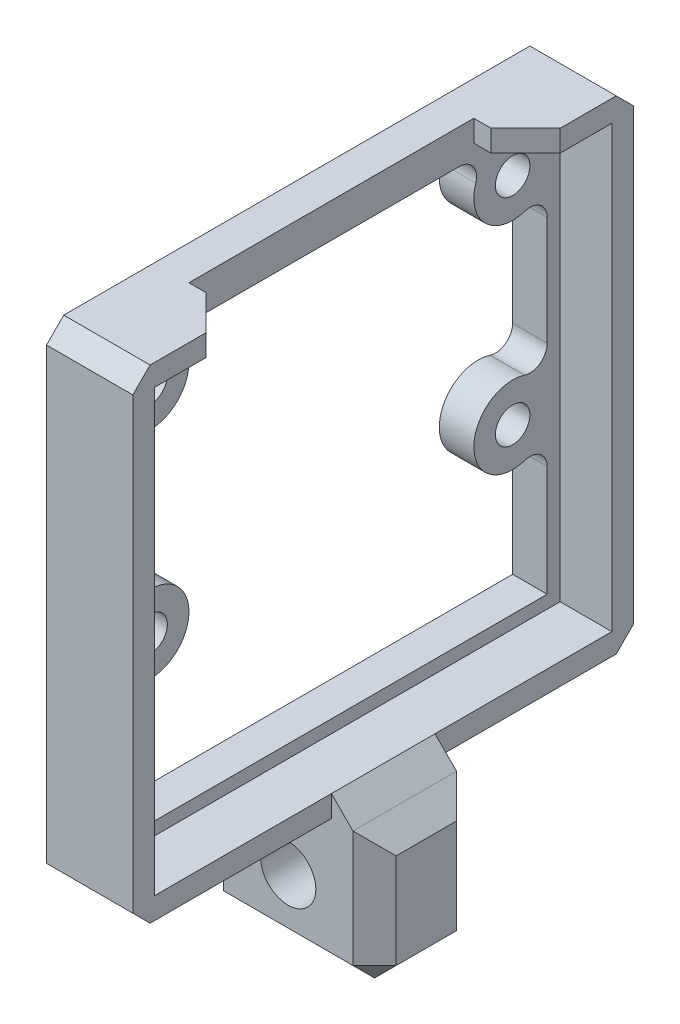
SolidWorks part; units mm, degrees
ref_plane "Front Plane" through (0, 0, 0) normal (0, 0, 1) x (1, 0, 0)
ref_plane "Top Plane" through (0, 0, 0) normal (0, 1, 0) x (1, 0, 0)
ref_plane "Right Plane" through (0, 0, 0) normal (1, 0, 0) x (0, 0, -1)
sketch "Sketch1" plane through (0, 0, 0) normal (1, 0, 0) x (0, 0, -1)
  line L0 (10.4772, -6.2072) -> (-10.5228, -6.2072) construction
  line L1 (10.4772, -6.2072) -> (10.4772, 6.2928) construction
  line L2 (10.4772, 6.2928) -> (-10.5228, 6.2928) construction
  line L3 (-10.5228, -6.2072) -> (-10.5228, 6.2928) construction
  line L4 (10.4772, -6.2072) -> (-10.5228, 6.2928) construction
  line L5 (-12.5228, 5.262) -> (-12.5228, -5.1764)
  line L6 (-12.5228, -7.238) -> (-12.5228, -13.7072)
  line L7 (-10.5228, -15.7072) -> (10.4772, -15.7072)
  line L8 (12.4772, -13.7072) -> (12.4772, -7.238)
  line L9 (12.4772, -5.1764) -> (12.4772, 5.262)
  line L10 (9.4464, 8.2928) -> (-9.4921, 8.2928)
  line L11 (10.4772, 6.2928) -> (-10.5228, -6.2072) construction
  line L12 (-14.5228, 10.2928) -> (-14.5228, -17.7072)
  line L13 (-12.5228, 8.2928) -> (12.4772, 8.2928)
  line L14 (-12.5228, 8.2928) -> (-12.5228, -15.7072)
  line L15 (-12.5228, -15.7072) -> (12.4772, -15.7072)
  line L16 (12.4772, 8.2928) -> (12.4772, -15.7072)
  line L17 (-12.5228, 8.2928) -> (12.4772, -15.7072) construction
  line L18 (-12.5228, -15.7072) -> (12.4772, 8.2928) construction
  line L19 (-14.5228, -17.7072) -> (14.4772, -17.7072)
  line L20 (14.4772, 10.2928) -> (14.4772, -17.7072)
  line L21 (-14.5228, 10.2928) -> (14.4772, 10.2928)
  circle A0 centre (10.4772, 6.2928) radius 1
  circle A1 centre (-10.5228, 6.2928) radius 1
  arc A2 (-12.5228, 5.262) -> (-9.4921, 8.2928) centre (-10.5228, 6.2928) ccw
  arc A3 (-12.5228, -7.238) -> (-12.5228, -5.1764) centre (-10.5228, -6.2072) ccw
  arc A4 (-12.5228, -13.7072) -> (-10.5228, -15.7072) centre (-10.5228, -13.7072) ccw
  arc A5 (10.4772, -15.7072) -> (12.4772, -13.7072) centre (10.4772, -13.7072) ccw
  arc A6 (12.4772, -5.1764) -> (12.4772, -7.238) centre (10.4772, -6.2072) ccw
  arc A7 (9.4464, 8.2928) -> (12.4772, 5.262) centre (10.4772, 6.2928) ccw
  circle A8 centre (-10.5228, -6.2072) radius 1
  circle A9 centre (10.4772, -6.2072) radius 1
  point P22 (-0.0228, 0.0428)
  point P28 (-0.0228, -3.7072)
  dimension "D1" = 2
  dimension "D2" = 2.25
  dimension "D3" = 2
  dimension "D4" = 9.4464
  dimension "D5" = 12.4772
  dimension "D6" = 0.0228
  dimension "D7" = 0.0428
  dimension "D8" = 5.262
  dimension "D9" = 15.7072
  dimension "D10" = 2
extrude "Boss-Extrude1" add sketch "Sketch1" along normal blind 2 contours L21 L12 L19 L20 L13 L16 L9 L8 L15 L7 L14 L6 L5 L10 | L14 A3 A8 | A1 | L14 A2 L13 A1 | L13 A7 L16 A0 | L16 A6 A9
sketch "Sketch2" plane through (2, 0, 0) normal (1, 0, 0) x (0, 0, -1)
  line L1 (-13.2728, 9.0428) -> (13.2272, 9.0428)
  line L2 (-13.2728, 9.0428) -> (-13.2728, -16.4572)
  line L3 (-13.2728, -16.4572) -> (13.2272, -16.4572)
  line L4 (14.4772, 10.2928) -> (-14.5228, 10.2928)
  line L5 (-14.5228, 10.2928) -> (-14.5228, -17.7072)
  line L6 (-14.5228, -17.7072) -> (14.4772, -17.7072)
  line L7 (14.4772, -17.7072) -> (14.4772, 10.2928)
  line L8 (14.4772, 10.2928) -> (-14.5228, 10.2928)
  line L9 (-14.5228, 10.2928) -> (-14.5228, -17.7072)
  line L10 (-14.5228, -17.7072) -> (14.4772, -17.7072)
  line L11 (14.4772, -17.7072) -> (14.4772, 10.2928)
  line L12 (13.2272, 9.0428) -> (13.2272, -16.4572)
  line L13 (-13.2728, 9.0428) -> (13.2272, -16.4572) construction
  line L14 (-13.2728, -16.4572) -> (13.2272, 9.0428) construction
  point P8 (-0.0228, -3.7072)
  dimension "D2" = 25.5
  dimension "D3" = 26.5
  dimension "D4" = 1.25
  dimension "D5" = 1.25
  dimension "D1" = 0
extrude "Boss-Extrude2" add sketch "Sketch2" along normal blind 3
fillet "Fillet1" radius 1 8 edges at (1, -5.1764, 12.5228) (1, -7.238, 12.5228) (1, 5.262, 12.5228) (1, 8.2928, 9.4921) (1, 8.2928, -9.4464) (1, 5.262, -12.4772) (1, -7.238, -12.4772) (1, -5.1764, -12.4772)
sketch "Sketch3" plane through (0, 0, 0) normal (-1, 0, 0) x (0, 0, 1)
  line L0 (14.5228, -17.7072) -> (-14.4772, -17.7072) construction
  line L1 (-2.9772, -17.7072) -> (3.0228, -17.7072)
  line L2 (-2.9772, -17.7072) -> (-2.9772, -25.7072)
  line L3 (-2.9772, -25.7072) -> (3.0228, -25.7072)
  line L4 (3.0228, -17.7072) -> (3.0228, -25.7072)
  line L5 (-2.9772, -17.7072) -> (3.0228, -25.7072) construction
  line L6 (-2.9772, -25.7072) -> (3.0228, -17.7072) construction
  point P4 (0.0228, -21.7072)
  point P7 (13.9832, -21.7072)
  point P8 (0.0228, -17.7072)
  point P9 (0.0228, -17.7072)
  dimension "D1" = 8
  dimension "D2" = 6
extrude "Boss-Extrude3" add sketch "Sketch3" along normal blind 2.5 and the other way blind 7.5
chamfer "Chamfer1" distance 1.25 angle 45 12 edges at (2.5, -25.7072, -2.9772) (-2.5, -17.7072, 0.0228) (-2.5, -21.7072, 3.0228) (-2.5, -21.7072, -2.9772) (-2.5, -25.7072, 0.0228) (2.5, -25.7072, 3.0228) (7.5, -25.7072, 0.0228) (7.5, -21.7072, 3.0228) (7.5, -17.7072, 0.0228) (7.5, -21.7072, -2.9772) (5, -17.7072, 0.0228) (0, -17.7072, 0.0228)
sketch "Sketch5" plane through (0, 0, -2.9772) normal (0, 0, -1) x (-1, 0, 0)
  line L0 (2.5, -18.9572) -> (2.5, -24.4572) construction
  line L1 (1.25, -25.7072) -> (-6.25, -25.7072) construction
  circle A0 centre (-2.5, -21.7072) radius 1.6
  dimension "D1" = 3.2
  dimension "D2" = 5
  dimension "D3" = 4
extrude "Cut-Extrude1" cut sketch "Sketch5" against normal through all both and the other way through all
sketch "Sketch7" plane through (0, 9.0428, 0) normal (0, -1, 0) x (1, 0, 0)
  line L0 (2, 8.2728) -> (5, 8.2728)
  line L1 (2, -8.2272) -> (5, -8.2272)
  line L4 (2, 13.2728) -> (2, -13.2272)
  line L5 (2, -13.2272) -> (5, -13.2272)
  line L6 (5, -13.2272) -> (5, 13.2728)
  line L7 (5, 13.2728) -> (2, 13.2728)
  line L8 (2, 13.2728) -> (2, -13.2272)
  line L9 (2, -13.2272) -> (5, -13.2272)
  line L10 (5, -13.2272) -> (5, 13.2728)
  line L11 (5, 13.2728) -> (2, 13.2728)
  line M7 (2, 13.2728) -> (2, -13.2272)
  line M9 (5, -13.2272) -> (5, 13.2728)
  dimension "D2" = 5
  dimension "D3" = 5
  dimension "D1" = 0
extrude "Cut-Extrude2" cut sketch "Sketch7" against normal through all contours L1 L0 M7 M9
chamfer "Chamfer2" distance 2 angle 45 2 edges at (5, 9.6678, -8.2272) (5, 9.6678, 8.2728)
chamfer "Chamfer3" distance 1 angle 45 4 edges at (2.5, 10.2928, -14.4772) (2.5, -17.7072, -14.4772) (2.5, -17.7072, 14.5228) (2.5, 10.2928, 14.5228)
